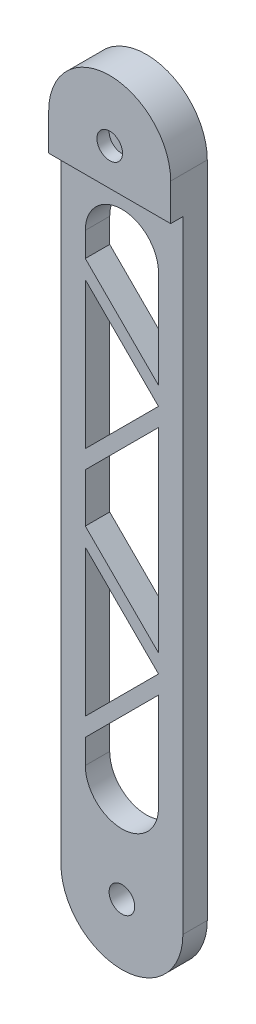
SolidWorks part; units mm, degrees
material "PLA"
ref_plane "Alzado" through (0, 0, 0) normal (0, 0, 1) x (1, 0, 0)
ref_plane "Planta" through (0, 0, 0) normal (0, 1, 0) x (1, 0, 0)
ref_plane "Vista lateral" through (0, 0, 0) normal (1, 0, 0) x (0, 0, -1)
sketch "Croquis1" plane through (0, 0, 0) normal (0, 0, 1) x (1, 0, 0)
  line L0 (0, 54) -> (0, -54) construction
  line L1 (10, 54) -> (10, -54)
  line L2 (-10, 54) -> (-10, -54)
  line L3 (0, 38) -> (0, -38) construction
  line L4 (6, 38) -> (6, -38)
  line L5 (-6, 38) -> (-6, -38)
  line L6 (-10, -47.95) -> (10, -47.95)
  line L7 (0, 51.9) -> (0, 44) construction
  line L8 (-10, 47.95) -> (10, 47.95)
  line L9 (0, -51.9) -> (0, -44) construction
  line L10 (0, 0) -> (0, -38) construction
  line L11 (-6, 0) -> (6, 0) construction
  line L12 (-6, -34) -> (6, -22)
  line L13 (-6, -31) -> (6, -19)
  line L14 (-6, -19) -> (6, -19) construction
  line L16 (-6, -7) -> (6, -19)
  line L17 (-6, -4) -> (6, -16)
  line L18 (-6, 4) -> (6, 16)
  line L19 (-6, 7) -> (6, 19)
  line L20 (-6, 31) -> (6, 19)
  line L21 (-6, 34) -> (6, 22)
  arc A0 (10, 54) -> (-10, 54) centre (0, 54) ccw
  arc A1 (-10, -54) -> (10, -54) centre (0, -54) ccw
  circle A2 centre (0, 54) radius 2.1
  circle A3 centre (0, -54) radius 2.1
  arc A4 (6, 38) -> (-6, 38) centre (0, 38) ccw
  arc A5 (-6, -38) -> (6, -38) centre (0, -38) ccw
  point P2 (0, 0)
  point P14 (0, 0)
  point P23 (0, 47.95)
  point P28 (0, -47.95)
  point P37 (0, -19)
  dimension "D1" = 4.2
  dimension "D2" = 20
  dimension "D3" = 108
  dimension "D4" = 4
  dimension "D5" = 16
  dimension "D6" = 135
  dimension "D7" = 3
extrude "Saliente-Extruir1" add sketch "Croquis1" along normal blind 4 contours L2 A1 L1 L8 A5 L5 A4 L4 A3 | L13 L5 L12 L4 | L17 L5 L16 L4 | L19 L5 L18 L4 | L21 L5 L20 L4 | L2 A1 L1 A0 | A3 | L5 A5 L4 A4 region at (9.0204, 0, 0) region at (0, 26.5, 0) region at (0, 11.5, 0) region at (0, -11.5, 0) region at (0, -26.5, 0)
extrude "Saliente-Extruir3" add sketch "Croquis1<6>" along normal blind 6 contours L1 A0 L2 L8 A2 region at (9.7436, 50.975, 0)
sketch "Croquis1<6>" plane through (0, 0, 0) normal (0, 0, 1) x (1, 0, 0) same geometry as "Croquis1"
